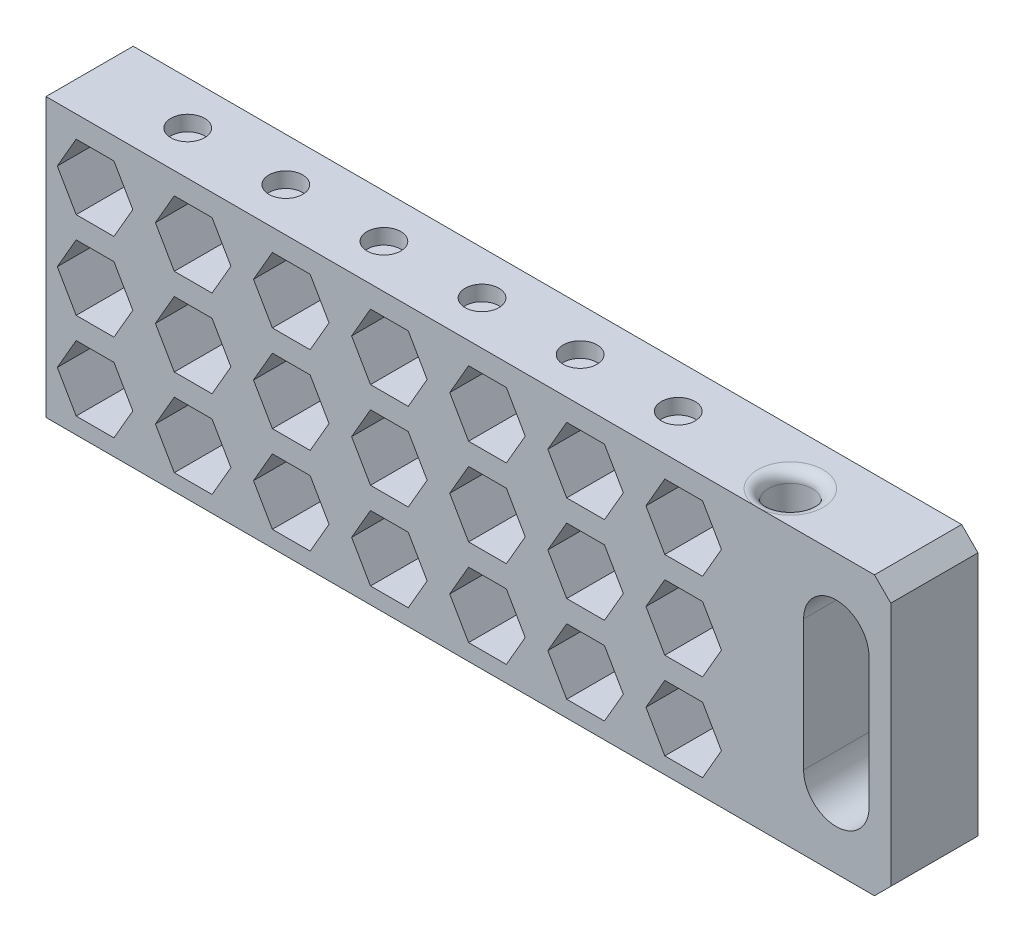
SolidWorks part; units mm, degrees
ref_plane "Front Plane" through (0, 0, 0) normal (0, 0, 1) x (1, 0, 0)
ref_plane "Top Plane" through (0, 0, 0) normal (0, 1, 0) x (1, 0, 0)
ref_plane "Right Plane" through (0, 0, 0) normal (1, 0, 0) x (0, 0, -1)
sketch "Sketch1" plane through (0, 0, 0) normal (0, 1, 0) x (1, 0, 0)
  line L1 (0, 0) -> (330, 0)
  line L2 (0, 0) -> (0, 16)
  line L3 (0, 16) -> (330, 16)
  line L4 (330, 0) -> (330, 16)
  dimension "D1" = 16
  dimension "D2" = 330
extrude "Boss-Extrude1" add sketch "Sketch1" along normal blind 51
sketch "Sketch2" plane through (0, 51, 0) normal (0, 1, 0) x (1, 0, 0)
  line L0 (0, 6) -> (330, 6) construction
  line L1 (0, 16) -> (0, 0) construction
  line L2 (330, 0) -> (330, 16) construction
  line L3 (0, 0) -> (330, 0) construction
  circle A0 centre (23, 6) radius 4
  circle A1 centre (305.575, 6) radius 4
  dimension "D2" = 8
  dimension "D1" = 23
  dimension "D3" = 6
  dimension "D4" = 282.575
extrude "Cut-Extrude1" cut sketch "Sketch2" against normal up to next
sketch "Sketch3" plane through (0, 0, 0) normal (0, 0, 1) x (1, 0, 0)
  line L0 (0, 51) -> (330, 51) construction
  line L1 (43.4641, 35) -> (46.9282, 41)
  line L2 (46.9282, 41) -> (43.4641, 47)
  line L3 (43.4641, 47) -> (36.5359, 47)
  line L4 (36.5359, 47) -> (33.0718, 41)
  line L5 (33.0718, 41) -> (36.5359, 35)
  line L6 (36.5359, 35) -> (43.4641, 35)
  line L7 (0, 51) -> (0, 0) construction
  line L8 (61.4641, 35) -> (64.9282, 41)
  line L9 (64.9282, 41) -> (61.4641, 47)
  line L10 (61.4641, 47) -> (54.5359, 47)
  line L11 (54.5359, 47) -> (51.0718, 41)
  line L12 (51.0718, 41) -> (54.5359, 35)
  line L13 (54.5359, 35) -> (61.4641, 35)
  line L14 (79.4641, 35) -> (82.9282, 41)
  line L15 (82.9282, 41) -> (79.4641, 47)
  line L16 (79.4641, 47) -> (72.5359, 47)
  line L17 (72.5359, 47) -> (69.0718, 41)
  line L18 (69.0718, 41) -> (72.5359, 35)
  line L19 (72.5359, 35) -> (79.4641, 35)
  line L20 (97.4641, 35) -> (100.9282, 41)
  line L21 (100.9282, 41) -> (97.4641, 47)
  line L22 (97.4641, 47) -> (90.5359, 47)
  line L23 (90.5359, 47) -> (87.0718, 41)
  line L24 (87.0718, 41) -> (90.5359, 35)
  line L25 (90.5359, 35) -> (97.4641, 35)
  line L26 (115.4641, 35) -> (118.9282, 41)
  line L27 (118.9282, 41) -> (115.4641, 47)
  line L28 (115.4641, 47) -> (108.5359, 47)
  line L29 (108.5359, 47) -> (105.0718, 41)
  line L30 (105.0718, 41) -> (108.5359, 35)
  line L31 (108.5359, 35) -> (115.4641, 35)
  line L32 (133.4641, 35) -> (136.9282, 41)
  line L33 (136.9282, 41) -> (133.4641, 47)
  line L34 (133.4641, 47) -> (126.5359, 47)
  line L35 (126.5359, 47) -> (123.0718, 41)
  line L36 (123.0718, 41) -> (126.5359, 35)
  line L37 (126.5359, 35) -> (133.4641, 35)
  line L38 (151.4641, 35) -> (154.9282, 41)
  line L39 (154.9282, 41) -> (151.4641, 47)
  line L40 (151.4641, 47) -> (144.5359, 47)
  line L41 (144.5359, 47) -> (141.0718, 41)
  line L42 (141.0718, 41) -> (144.5359, 35)
  line L43 (144.5359, 35) -> (151.4641, 35)
  line L44 (169.4641, 35) -> (172.9282, 41)
  line L45 (172.9282, 41) -> (169.4641, 47)
  line L46 (169.4641, 47) -> (162.5359, 47)
  line L47 (162.5359, 47) -> (159.0718, 41)
  line L48 (159.0718, 41) -> (162.5359, 35)
  line L49 (162.5359, 35) -> (169.4641, 35)
  line L50 (187.4641, 35) -> (190.9282, 41)
  line L51 (190.9282, 41) -> (187.4641, 47)
  line L52 (187.4641, 47) -> (180.5359, 47)
  line L53 (180.5359, 47) -> (177.0718, 41)
  line L54 (177.0718, 41) -> (180.5359, 35)
  line L55 (180.5359, 35) -> (187.4641, 35)
  line L56 (205.4641, 35) -> (208.9282, 41)
  line L57 (208.9282, 41) -> (205.4641, 47)
  line L58 (205.4641, 47) -> (198.5359, 47)
  line L59 (198.5359, 47) -> (195.0718, 41)
  line L60 (195.0718, 41) -> (198.5359, 35)
  line L61 (198.5359, 35) -> (205.4641, 35)
  line L62 (223.4641, 35) -> (226.9282, 41)
  line L63 (226.9282, 41) -> (223.4641, 47)
  line L64 (223.4641, 47) -> (216.5359, 47)
  line L65 (216.5359, 47) -> (213.0718, 41)
  line L66 (213.0718, 41) -> (216.5359, 35)
  line L67 (216.5359, 35) -> (223.4641, 35)
  line L68 (241.4641, 35) -> (244.9282, 41)
  line L69 (244.9282, 41) -> (241.4641, 47)
  line L70 (241.4641, 47) -> (234.5359, 47)
  line L71 (234.5359, 47) -> (231.0718, 41)
  line L72 (231.0718, 41) -> (234.5359, 35)
  line L73 (234.5359, 35) -> (241.4641, 35)
  line L74 (259.4641, 35) -> (262.9282, 41)
  line L75 (262.9282, 41) -> (259.4641, 47)
  line L76 (259.4641, 47) -> (252.5359, 47)
  line L77 (252.5359, 47) -> (249.0718, 41)
  line L78 (249.0718, 41) -> (252.5359, 35)
  line L79 (252.5359, 35) -> (259.4641, 35)
  line L80 (277.4641, 35) -> (280.9282, 41)
  line L81 (280.9282, 41) -> (277.4641, 47)
  line L82 (277.4641, 47) -> (270.5359, 47)
  line L83 (270.5359, 47) -> (267.0718, 41)
  line L84 (267.0718, 41) -> (270.5359, 35)
  line L85 (270.5359, 35) -> (277.4641, 35)
  line L86 (295.4641, 35) -> (298.9282, 41)
  line L87 (298.9282, 41) -> (295.4641, 47)
  line L88 (295.4641, 47) -> (288.5359, 47)
  line L89 (288.5359, 47) -> (285.0718, 41)
  line L90 (285.0718, 41) -> (288.5359, 35)
  line L91 (288.5359, 35) -> (295.4641, 35)
  line L92 (61.4641, 19) -> (64.9282, 25)
  line L93 (64.9282, 25) -> (61.4641, 31)
  line L94 (61.4641, 31) -> (54.5359, 31)
  line L95 (54.5359, 31) -> (51.0718, 25)
  line L96 (51.0718, 25) -> (54.5359, 19)
  line L97 (54.5359, 19) -> (61.4641, 19)
  line L98 (79.4641, 19) -> (82.9282, 25)
  line L99 (82.9282, 25) -> (79.4641, 31)
  line L100 (79.4641, 31) -> (72.5359, 31)
  line L101 (72.5359, 31) -> (69.0718, 25)
  line L102 (69.0718, 25) -> (72.5359, 19)
  line L103 (72.5359, 19) -> (79.4641, 19)
  line L104 (97.4641, 19) -> (100.9282, 25)
  line L105 (100.9282, 25) -> (97.4641, 31)
  line L106 (97.4641, 31) -> (90.5359, 31)
  line L107 (90.5359, 31) -> (87.0718, 25)
  line L108 (87.0718, 25) -> (90.5359, 19)
  line L109 (90.5359, 19) -> (97.4641, 19)
  line L110 (115.4641, 19) -> (118.9282, 25)
  line L111 (118.9282, 25) -> (115.4641, 31)
  line L112 (115.4641, 31) -> (108.5359, 31)
  line L113 (108.5359, 31) -> (105.0718, 25)
  line L114 (105.0718, 25) -> (108.5359, 19)
  line L115 (108.5359, 19) -> (115.4641, 19)
  line L116 (133.4641, 19) -> (136.9282, 25)
  line L117 (136.9282, 25) -> (133.4641, 31)
  line L118 (133.4641, 31) -> (126.5359, 31)
  line L119 (126.5359, 31) -> (123.0718, 25)
  line L120 (123.0718, 25) -> (126.5359, 19)
  line L121 (126.5359, 19) -> (133.4641, 19)
  line L122 (151.4641, 19) -> (154.9282, 25)
  line L123 (154.9282, 25) -> (151.4641, 31)
  line L124 (151.4641, 31) -> (144.5359, 31)
  line L125 (144.5359, 31) -> (141.0718, 25)
  line L126 (141.0718, 25) -> (144.5359, 19)
  line L127 (144.5359, 19) -> (151.4641, 19)
  line L128 (169.4641, 19) -> (172.9282, 25)
  line L129 (172.9282, 25) -> (169.4641, 31)
  line L130 (169.4641, 31) -> (162.5359, 31)
  line L131 (162.5359, 31) -> (159.0718, 25)
  line L132 (159.0718, 25) -> (162.5359, 19)
  line L133 (162.5359, 19) -> (169.4641, 19)
  line L134 (187.4641, 19) -> (190.9282, 25)
  line L135 (190.9282, 25) -> (187.4641, 31)
  line L136 (187.4641, 31) -> (180.5359, 31)
  line L137 (180.5359, 31) -> (177.0718, 25)
  line L138 (177.0718, 25) -> (180.5359, 19)
  line L139 (180.5359, 19) -> (187.4641, 19)
  line L140 (205.4641, 19) -> (208.9282, 25)
  line L141 (208.9282, 25) -> (205.4641, 31)
  line L142 (205.4641, 31) -> (198.5359, 31)
  line L143 (198.5359, 31) -> (195.0718, 25)
  line L144 (195.0718, 25) -> (198.5359, 19)
  line L145 (198.5359, 19) -> (205.4641, 19)
  line L146 (223.4641, 19) -> (226.9282, 25)
  line L147 (226.9282, 25) -> (223.4641, 31)
  line L148 (223.4641, 31) -> (216.5359, 31)
  line L149 (216.5359, 31) -> (213.0718, 25)
  line L150 (213.0718, 25) -> (216.5359, 19)
  line L151 (216.5359, 19) -> (223.4641, 19)
  line L152 (241.4641, 19) -> (244.9282, 25)
  line L153 (244.9282, 25) -> (241.4641, 31)
  line L154 (241.4641, 31) -> (234.5359, 31)
  line L155 (234.5359, 31) -> (231.0718, 25)
  line L156 (231.0718, 25) -> (234.5359, 19)
  line L157 (234.5359, 19) -> (241.4641, 19)
  line L158 (259.4641, 19) -> (262.9282, 25)
  line L159 (262.9282, 25) -> (259.4641, 31)
  line L160 (259.4641, 31) -> (252.5359, 31)
  line L161 (252.5359, 31) -> (249.0718, 25)
  line L162 (249.0718, 25) -> (252.5359, 19)
  line L163 (252.5359, 19) -> (259.4641, 19)
  line L164 (277.4641, 19) -> (280.9282, 25)
  line L165 (280.9282, 25) -> (277.4641, 31)
  line L166 (277.4641, 31) -> (270.5359, 31)
  line L167 (270.5359, 31) -> (267.0718, 25)
  line L168 (267.0718, 25) -> (270.5359, 19)
  line L169 (270.5359, 19) -> (277.4641, 19)
  line L170 (295.4641, 19) -> (298.9282, 25)
  line L171 (298.9282, 25) -> (295.4641, 31)
  line L172 (295.4641, 31) -> (288.5359, 31)
  line L173 (288.5359, 31) -> (285.0718, 25)
  line L174 (285.0718, 25) -> (288.5359, 19)
  line L175 (288.5359, 19) -> (295.4641, 19)
  line L176 (61.4641, 3) -> (64.9282, 9)
  line L177 (64.9282, 9) -> (61.4641, 15)
  line L178 (61.4641, 15) -> (54.5359, 15)
  line L179 (54.5359, 15) -> (51.0718, 9)
  line L180 (51.0718, 9) -> (54.5359, 3)
  line L181 (54.5359, 3) -> (61.4641, 3)
  line L182 (79.4641, 3) -> (82.9282, 9)
  line L183 (82.9282, 9) -> (79.4641, 15)
  line L184 (79.4641, 15) -> (72.5359, 15)
  line L185 (72.5359, 15) -> (69.0718, 9)
  line L186 (69.0718, 9) -> (72.5359, 3)
  line L187 (72.5359, 3) -> (79.4641, 3)
  line L188 (97.4641, 3) -> (100.9282, 9)
  line L189 (100.9282, 9) -> (97.4641, 15)
  line L190 (97.4641, 15) -> (90.5359, 15)
  line L191 (90.5359, 15) -> (87.0718, 9)
  line L192 (87.0718, 9) -> (90.5359, 3)
  line L193 (90.5359, 3) -> (97.4641, 3)
  line L194 (115.4641, 3) -> (118.9282, 9)
  line L195 (118.9282, 9) -> (115.4641, 15)
  line L196 (115.4641, 15) -> (108.5359, 15)
  line L197 (108.5359, 15) -> (105.0718, 9)
  line L198 (105.0718, 9) -> (108.5359, 3)
  line L199 (108.5359, 3) -> (115.4641, 3)
  line L200 (133.4641, 3) -> (136.9282, 9)
  line L201 (136.9282, 9) -> (133.4641, 15)
  line L202 (133.4641, 15) -> (126.5359, 15)
  line L203 (126.5359, 15) -> (123.0718, 9)
  line L204 (123.0718, 9) -> (126.5359, 3)
  line L205 (126.5359, 3) -> (133.4641, 3)
  line L206 (151.4641, 3) -> (154.9282, 9)
  line L207 (154.9282, 9) -> (151.4641, 15)
  line L208 (151.4641, 15) -> (144.5359, 15)
  line L209 (144.5359, 15) -> (141.0718, 9)
  line L210 (141.0718, 9) -> (144.5359, 3)
  line L211 (144.5359, 3) -> (151.4641, 3)
  line L212 (169.4641, 3) -> (172.9282, 9)
  line L213 (172.9282, 9) -> (169.4641, 15)
  line L214 (169.4641, 15) -> (162.5359, 15)
  line L215 (162.5359, 15) -> (159.0718, 9)
  line L216 (159.0718, 9) -> (162.5359, 3)
  line L217 (162.5359, 3) -> (169.4641, 3)
  line L218 (187.4641, 3) -> (190.9282, 9)
  line L219 (190.9282, 9) -> (187.4641, 15)
  line L220 (187.4641, 15) -> (180.5359, 15)
  line L221 (180.5359, 15) -> (177.0718, 9)
  line L222 (177.0718, 9) -> (180.5359, 3)
  line L223 (180.5359, 3) -> (187.4641, 3)
  line L224 (205.4641, 3) -> (208.9282, 9)
  line L225 (208.9282, 9) -> (205.4641, 15)
  line L226 (205.4641, 15) -> (198.5359, 15)
  line L227 (198.5359, 15) -> (195.0718, 9)
  line L228 (195.0718, 9) -> (198.5359, 3)
  line L229 (198.5359, 3) -> (205.4641, 3)
  line L230 (223.4641, 3) -> (226.9282, 9)
  line L231 (226.9282, 9) -> (223.4641, 15)
  line L232 (223.4641, 15) -> (216.5359, 15)
  line L233 (216.5359, 15) -> (213.0718, 9)
  line L234 (213.0718, 9) -> (216.5359, 3)
  line L235 (216.5359, 3) -> (223.4641, 3)
  line L236 (241.4641, 3) -> (244.9282, 9)
  line L237 (244.9282, 9) -> (241.4641, 15)
  line L238 (241.4641, 15) -> (234.5359, 15)
  line L239 (234.5359, 15) -> (231.0718, 9)
  line L240 (231.0718, 9) -> (234.5359, 3)
  line L241 (234.5359, 3) -> (241.4641, 3)
  line L242 (259.4641, 3) -> (262.9282, 9)
  line L243 (262.9282, 9) -> (259.4641, 15)
  line L244 (259.4641, 15) -> (252.5359, 15)
  line L245 (252.5359, 15) -> (249.0718, 9)
  line L246 (249.0718, 9) -> (252.5359, 3)
  line L247 (252.5359, 3) -> (259.4641, 3)
  line L248 (277.4641, 3) -> (280.9282, 9)
  line L249 (280.9282, 9) -> (277.4641, 15)
  line L250 (277.4641, 15) -> (270.5359, 15)
  line L251 (270.5359, 15) -> (267.0718, 9)
  line L252 (267.0718, 9) -> (270.5359, 3)
  line L253 (270.5359, 3) -> (277.4641, 3)
  line L254 (295.4641, 3) -> (298.9282, 9)
  line L255 (298.9282, 9) -> (295.4641, 15)
  line L256 (295.4641, 15) -> (288.5359, 15)
  line L257 (288.5359, 15) -> (285.0718, 9)
  line L258 (285.0718, 9) -> (288.5359, 3)
  line L259 (288.5359, 3) -> (295.4641, 3)
  line L260 (43.4641, 19) -> (46.9282, 25)
  line L261 (46.9282, 25) -> (43.4641, 31)
  line L262 (43.4641, 31) -> (36.5359, 31)
  line L263 (36.5359, 31) -> (33.0718, 25)
  line L264 (33.0718, 25) -> (36.5359, 19)
  line L265 (36.5359, 19) -> (43.4641, 19)
  line L266 (43.4641, 3) -> (46.9282, 9)
  line L267 (46.9282, 9) -> (43.4641, 15)
  line L268 (43.4641, 15) -> (36.5359, 15)
  line L269 (36.5359, 15) -> (33.0718, 9)
  line L270 (33.0718, 9) -> (36.5359, 3)
  line L271 (36.5359, 3) -> (43.4641, 3)
  circle A0 centre (40, 41) radius 6 construction
  dimension "D1" = 12
  dimension "D2" = 40
  dimension "D3" = 10
  dimension "D4" = 15
  dimension "D5" = 3
extrude "Cut-Extrude2" cut sketch "Sketch3" against normal up to next (16 mm away)
sketch "Sketch4" plane through (0, 0, 0) normal (0, 0, 1) x (1, 0, 0)
  line L0 (10, 13.5) -> (10, 37.5) construction
  line L1 (4, 13.5) -> (4, 37.5)
  line L2 (16, 13.5) -> (16, 37.5)
  line L3 (0, 51) -> (0, 0) construction
  line L4 (165, 51) -> (165, 0) construction
  line L5 (0, 51) -> (330, 51) construction
  line L6 (0, 0) -> (330, 0) construction
  line L7 (320, 13.5) -> (320, 37.5) construction
  line L8 (326, 13.5) -> (326, 37.5)
  line L9 (314, 13.5) -> (314, 37.5)
  arc A0 (4, 13.5) -> (16, 13.5) centre (10, 13.5) ccw
  arc A1 (16, 37.5) -> (4, 37.5) centre (10, 37.5) ccw
  arc A2 (326, 13.5) -> (314, 13.5) centre (320, 13.5) cw
  arc A3 (314, 37.5) -> (326, 37.5) centre (320, 37.5) cw
  point P2 (10, 25.5)
  point P9 (0, 25.5)
  point P18 (320, 25.5)
  dimension "D1" = 24
  dimension "D2" = 10
  dimension "D3" = 12
extrude "Cut-Extrude3" cut sketch "Sketch4" against normal up to next
sketch "Sketch5" plane through (0, 51, 0) normal (0, 1, 0) x (1, 0, 0)
  line L0 (0, 8) -> (330, 8) construction
  line L1 (0, 16) -> (0, 0) construction
  line L2 (330, 0) -> (330, 16) construction
  circle A0 centre (49, 8) radius 3.1
  circle A1 centre (67, 8) radius 3.1
  circle A2 centre (85, 8) radius 3.1
  circle A3 centre (103, 8) radius 3.1
  circle A4 centre (121, 8) radius 3.1
  circle A5 centre (139, 8) radius 3.1
  circle A6 centre (157, 8) radius 3.1
  circle A7 centre (175, 8) radius 3.1
  circle A8 centre (193, 8) radius 3.1
  circle A9 centre (211, 8) radius 3.1
  circle A10 centre (229, 8) radius 3.1
  circle A11 centre (247, 8) radius 3.1
  circle A12 centre (265, 8) radius 3.1
  circle A13 centre (283, 8) radius 3.1
  dimension "D1" = 6.2
  dimension "D2" = 49
  dimension "D3" = 14
extrude "Cut-Extrude4" cut sketch "Sketch5" against normal blind 2.8
sketch "Sketch6" plane through (0, 0, 0) normal (0, 0, 1) x (1, 0, 0)
  line L0 (0, 51) -> (330, 51) construction
  line L1 (0, 0) -> (175, 0)
  line L2 (0, 0) -> (0, 51)
  line L3 (0, 51) -> (175, 51)
  line L4 (175, 0) -> (175, 51)
  line L5 (172.9282, 25) -> (177.0718, 25) construction
  point P11 (175, 25)
extrude "Cut-Extrude5" cut sketch "Sketch6" against normal through all
sketch "Sketch7" plane through (0, 51, 0) normal (0, 1, 0) x (1, 0, 0)
  line L1 (175, 11.1) -> (175, 4.9)
  arc A1 (175, 4.9) -> (175, 11.1) centre (175, 8) ccw
  arc A2 (175, 4.9) -> (175, 11.1) centre (175, 8) ccw construction
  point P1 (0, 0)
extrude "Cover" add sketch "Sketch7" against normal up to surface (2.8 mm away) up to face at (193, 48.2, -4.9)
sketch "Sketch8" plane through (175, 0, 0) normal (-1, 0, 0) x (0, 0, 1)
  line L0 (-16, 51) -> (0, 51) construction
  line L1 (-12.05, 3.9) -> (-3.95, 3.9)
  line L2 (-12.05, 3.9) -> (-12.05, 47.1)
  line L3 (-12.05, 47.1) -> (-3.95, 47.1)
  line L4 (-3.95, 3.9) -> (-3.95, 47.1)
  line L5 (-16, 0) -> (0, 0) construction
  line L6 (-16, 0) -> (-16, 51) construction
  point P8 (-8, 3.9)
  dimension "D1" = 3.9
  dimension "D2" = 3.9
  dimension "D3" = 8.1
  dimension "D4" = 8
extrude "Cut-Extrude6" cut sketch "Sketch8" against normal blind 2
chamfer "Chamfer2" distance 3 angle 45 2 edges at (330, 51, -8) (330, 0, -8)
ref_plane "Plane1" through (0, 25.5, 0) normal (0, -1, 0) x (-1, 0, 0)
fillet "Fillet3" radius 2 1 edges at (305.575, 51, -2)
mirror "Mirror1" about plane through (0, 25.5, 0) normal (0, -1, 0) of "Cover", "Cut-Extrude4"
fillet "Fillet2" radius 2 4 edges at (175, 3.9, -8) (175, 25.5, -3.95) (175, 47.1, -8) (175, 25.5, -12.05)
fillet "Fillet4" radius 2 1 edges at (305.575, 0, -10)
